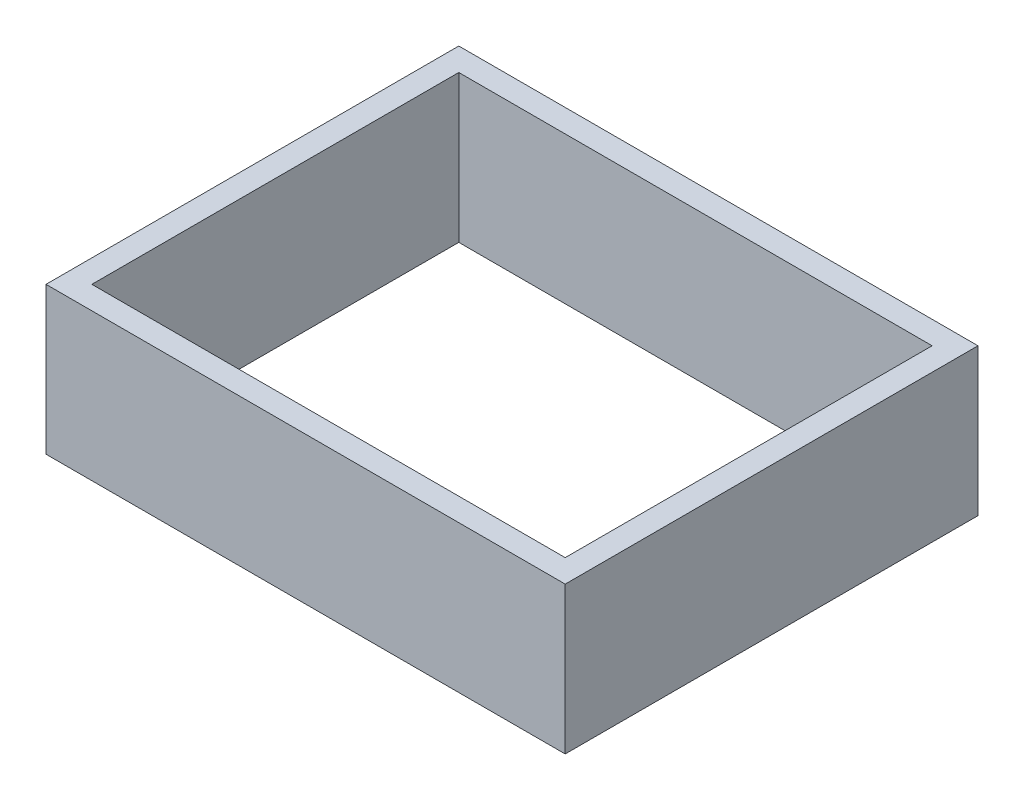
SolidWorks part; units mm, degrees
ref_plane "Front Plane" through (0, 0, 0) normal (0, 0, 1) x (1, 0, 0)
ref_plane "Top Plane" through (0, 0, 0) normal (0, 1, 0) x (1, 0, 0)
ref_plane "Right Plane" through (0, 0, 0) normal (1, 0, 0) x (0, 0, -1)
sketch "Sketch1" plane through (0, 0, 0) normal (0, 1, 0) x (1, 0, 0)
  line L1 (0, 0) -> (283, 0)
  line L2 (0, 0) -> (0, 225)
  line L3 (0, 225) -> (283, 225)
  line L4 (283, 0) -> (283, 225)
  dimension "D1" = 225
  dimension "D2" = 283
extrude "Boss-Extrude1" add sketch "Sketch1" along normal blind 80.2 contours L1 L4 L3 L2
sketch "Sketch2" plane through (0, 80.2, 0) normal (0, 1, 0) x (1, 0, 0)
  line L14 (12.5, 12.5) -> (270.5, 12.5)
  line L15 (270.5, 12.5) -> (270.5, 212.5)
  line L16 (270.5, 212.5) -> (12.5, 212.5)
  line L17 (12.5, 212.5) -> (12.5, 12.5)
  line L18 (12.5, 12.5) -> (270.5, 12.5)
  line L19 (270.5, 12.5) -> (270.5, 212.5)
  line L20 (270.5, 212.5) -> (12.5, 212.5)
  line L21 (12.5, 212.5) -> (12.5, 12.5)
  dimension "D1" = 12.5
extrude "Cut-Extrude1" cut sketch "Sketch2" against normal up to surface (80.2 mm away) contours L21 L18 L19 L20 up to face at (141.5, 0, -112.5)
equation "\"Length\" = 283mm"
equation "\"Width\" = 225mm"
equation "\"WallThickness\" = 12.5mm"
equation "\"UpperWaterJacketThickness\" = 28mm"
equation "\"D1@Sketch1\"=\"Width\""
equation "\"D2@Sketch1\"=\"Length\""
equation "\"SpacerHeight\" = 80.2mm"
equation "\"D1@Boss-Extrude1\"=\"SpacerHeight\""
equation "\"D1@Sketch2\"=\"WallThickness\""
